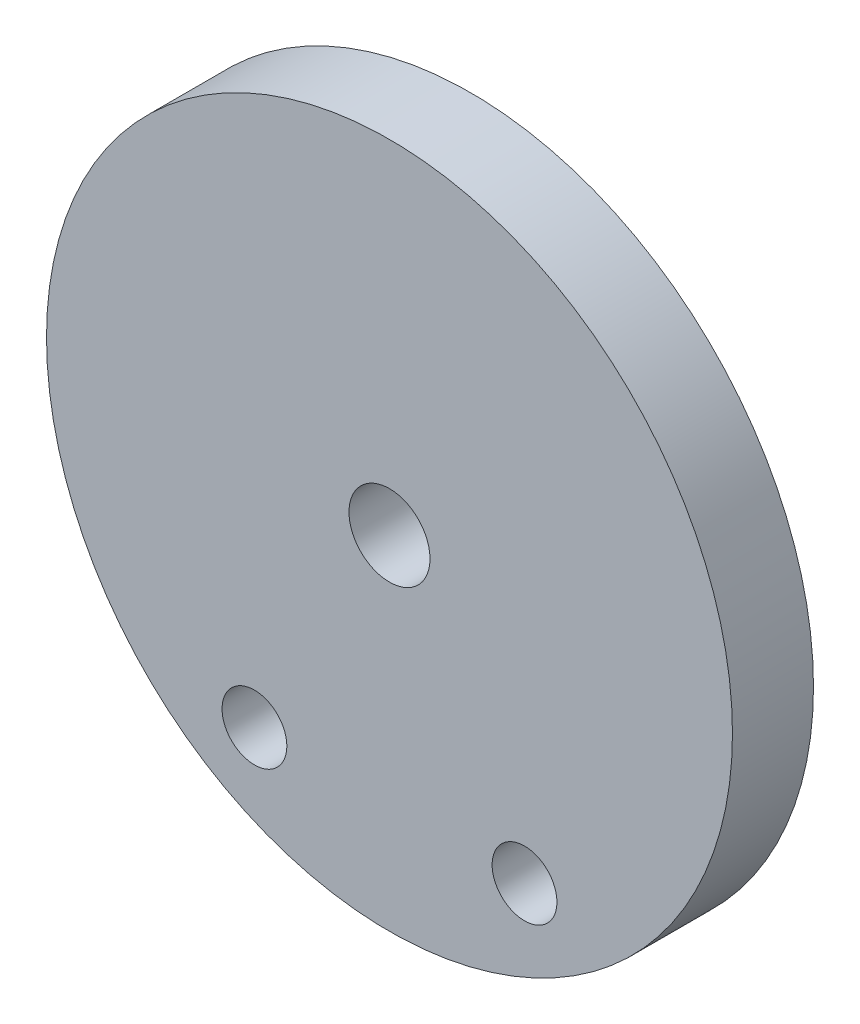
SolidWorks part; units mm, degrees
ref_plane "Front Plane" through (0, 0, 0) normal (0, 0, 1) x (1, 0, 0)
ref_plane "Top Plane" through (0, 0, 0) normal (0, 1, 0) x (1, 0, 0)
ref_plane "Right Plane" through (0, 0, 0) normal (1, 0, 0) x (0, 0, -1)
sketch "Sketch1" plane through (0, 0, 0) normal (0, 0, 1) x (1, 0, 0)
  circle A0 centre (0, 0) radius 12.7
  circle A1 centre (0, 0) radius 1.5
  circle A2 centre (5, -8.66) radius 1.2
  circle A3 centre (-5, -8.66) radius 1.2
extrude "Boss-Extrude1" add sketch "Sketch1" along normal blind 3
ref_axis "Hub" through (0, 0, 3.15) along (0, 0, -1)
ref_plane "Hole_R_px" through (-5, 0, 0) normal (1, 0, 0) x (0, 0, -1)
ref_plane "Hole_R_py" through (0, -8.66, 0) normal (0, 1, 0) x (1, 0, 0)
ref_axis "Hole_R" through (-5, -8.66, 3.15) along (0, 0, -1)
ref_plane "Hole_L_px" through (5, 0, 0) normal (1, 0, 0) x (0, 0, -1)
ref_plane "Hole_L_py" through (0, -8.66, 0) normal (0, 1, 0) x (1, 0, 0)
ref_axis "Hole_L" through (5, -8.66, 3.15) along (0, 0, -1)
ref_plane "Link_R" through (0, 0, 3) normal (0, 0, 1) x (1, 0, 0)
ref_plane "Link_L" through (0, 0, 3.6) normal (0, 0, 1) x (1, 0, 0)
